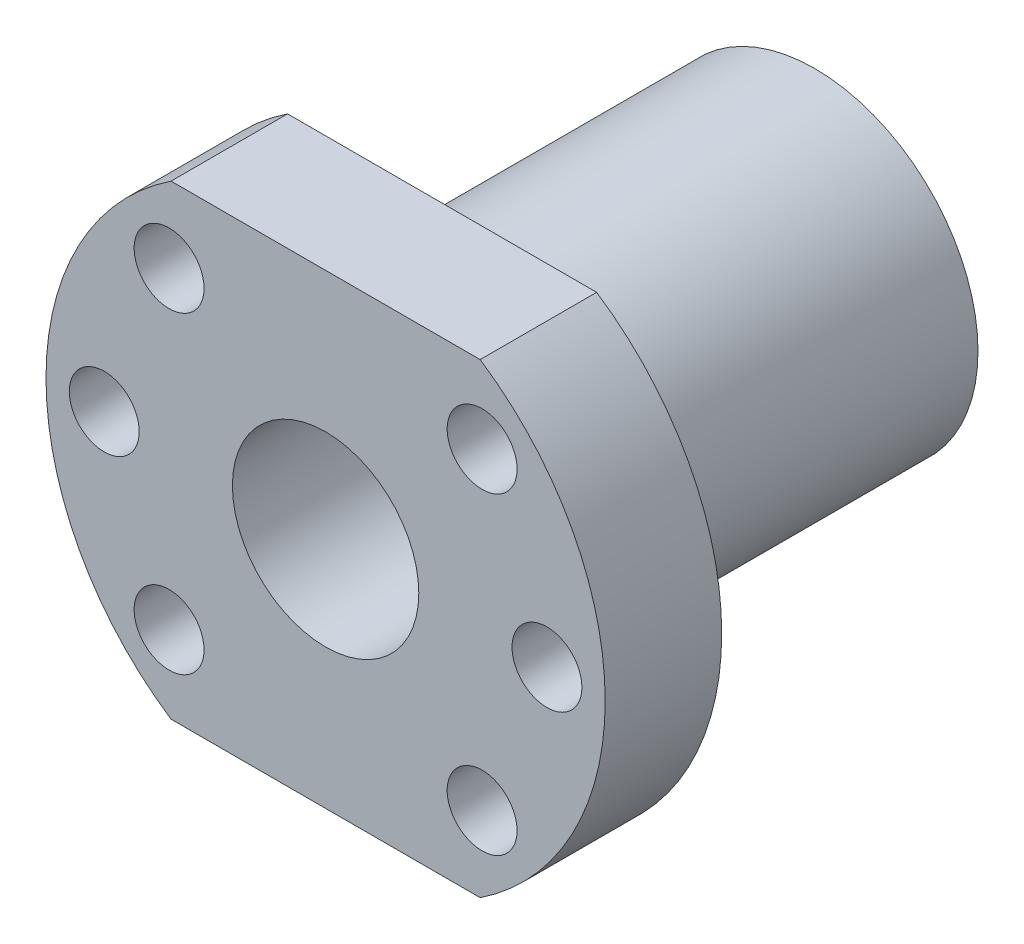
SolidWorks part; units mm, degrees
note: The reader was unsure of these and kept them because the rebuilt part matched: shared geometry of "Sketch1<3>".
ref_plane "Front Plane" through (0, 0, 0) normal (0, 0, 1) x (1, 0, 0)
ref_plane "Top Plane" through (0, 0, 0) normal (0, 1, 0) x (1, 0, 0)
ref_plane "Right Plane" through (0, 0, 0) normal (1, 0, 0) x (0, 0, -1)
sketch "Sketch1" plane through (0, 0, 0) normal (0, 0, 1) x (1, 0, 0)
  line L0 (-13.2665, -20) -> (13.2665, -20)
  line L2 (0, 0) -> (-24, 0) construction
  line L3 (-13.2665, 20) -> (13.2665, 20)
  arc A4 (13.2665, -20) -> (13.2665, 20) centre (0, 0) ccw
  arc A5 (-13.2665, 20) -> (-13.2665, -20) centre (0, 0) ccw
  circle A6 centre (0, 0) radius 14
  circle A7 centre (0, 0) radius 19 construction
  circle A8 centre (19, 0) radius 3
  circle A9 centre (13.435, -13.435) radius 3
  circle A10 centre (0, -19) radius 3 [skipped]
  circle A11 centre (-13.435, -13.435) radius 3
  circle A12 centre (-19, 0) radius 3
  circle A13 centre (-13.435, 13.435) radius 3
  circle A14 centre (0, 19) radius 3 [skipped]
  circle A15 centre (13.435, 13.435) radius 3
  circle A16 centre (0, 0) radius 8
  point P28 (0, 0)
  dimension "D2" = 24
  dimension "D3" = 28
  dimension "D4" = 38
  dimension "D6" = 6
  dimension "D7" = 16
  dimension "D1" = 20
  dimension "D5" = 8
extrude "Boss-Extrude1" add sketch "Sketch1" along normal blind 10 contours L3 A5 L0 A4 A15 A13 A12 A11 A9 A8 A6 | A6 A16
extrude "Boss-Extrude2" add sketch "Sketch1<3>" against normal blind 32 contours A6 A16
sketch "Sketch1<3>" plane through (0, 0, 0) normal (0, 0, 1) x (1, 0, 0) same geometry as "Sketch1"
